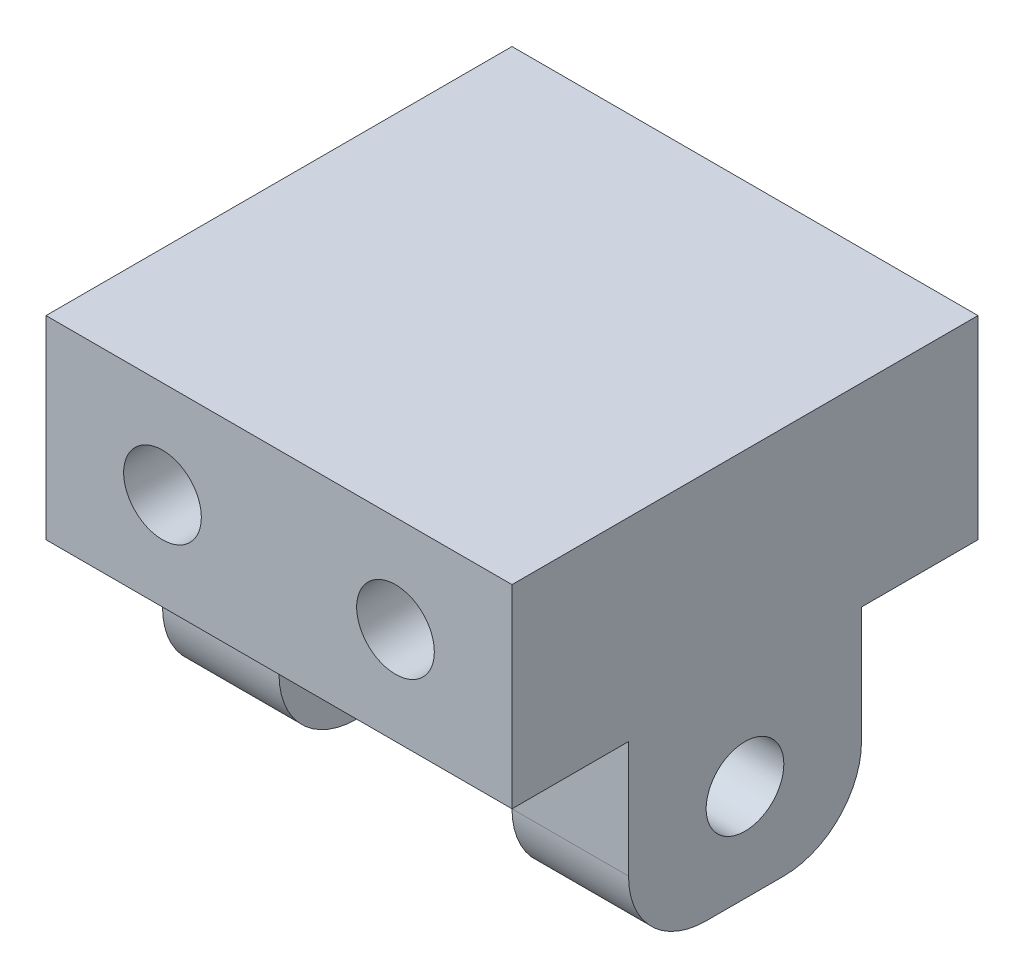
SolidWorks part; units mm, degrees
ref_plane "Front Plane" through (0, 0, 0) normal (0, 0, 1) x (1, 0, 0)
ref_plane "Top Plane" through (0, 0, 0) normal (0, 1, 0) x (1, 0, 0)
ref_plane "Right Plane" through (0, 0, 0) normal (1, 0, 0) x (0, 0, -1)
sketch "Sketch1" plane through (0, 0, 0) normal (0, 0, 1) x (1, 0, 0)
  line L1 (-6, 2.5) -> (6, 2.5)
  line L2 (-6, 2.5) -> (-6, -2.5)
  line L3 (-6, -2.5) -> (6, -2.5)
  line L4 (6, 2.5) -> (6, -2.5)
  point P4 (0, 2.5)
  point P6 (6, 0)
  dimension "D1" = 12
  dimension "D2" = 5
extrude "Boss-Extrude1" add sketch "Sketch1" along normal blind 6 and the other way blind 6
sketch "Sketch2" plane through (0, 0, 6) normal (0, 0, 1) x (1, 0, 0)
  circle A0 centre (-3, 0) radius 1
  circle A1 centre (3, 0) radius 1
  dimension "D1" = 2
  dimension "D2" = 2
  dimension "D3" = 3
  dimension "D4" = 3
extrude "Cut-Extrude1" cut sketch "Sketch2" against normal up to surface (12 mm away) up to face at (0, 0, -6)
sketch "Sketch3" plane through (6, 0, 0) normal (1, 0, 0) x (0, 0, -1)
  line L0 (6, -2.5) -> (-6, -2.5) construction
  line L1 (-3, -2.5) -> (3, -2.5)
  line L2 (-3, -2.5) -> (-3, -7.5)
  line L3 (-3, -7.5) -> (3, -7.5)
  line L4 (3, -2.5) -> (3, -7.5)
  circle A0 centre (0, -5) radius 1
  dimension "D1" = 2
  dimension "D3" = 2.5
  dimension "D5" = 3
  dimension "D2" = 5
  dimension "D4" = 6
  dimension "D6" = 3
extrude "Boss-Extrude2" add sketch "Sketch3" against normal blind 3
fillet "Fillet1" radius 2 2 edges at (4.5, -7.5, 3) (4.5, -7.5, -3)
mirror "Mirror1" about plane through (0, 0, 0) normal (1, 0, 0) of "Fillet1", "Boss-Extrude2"
